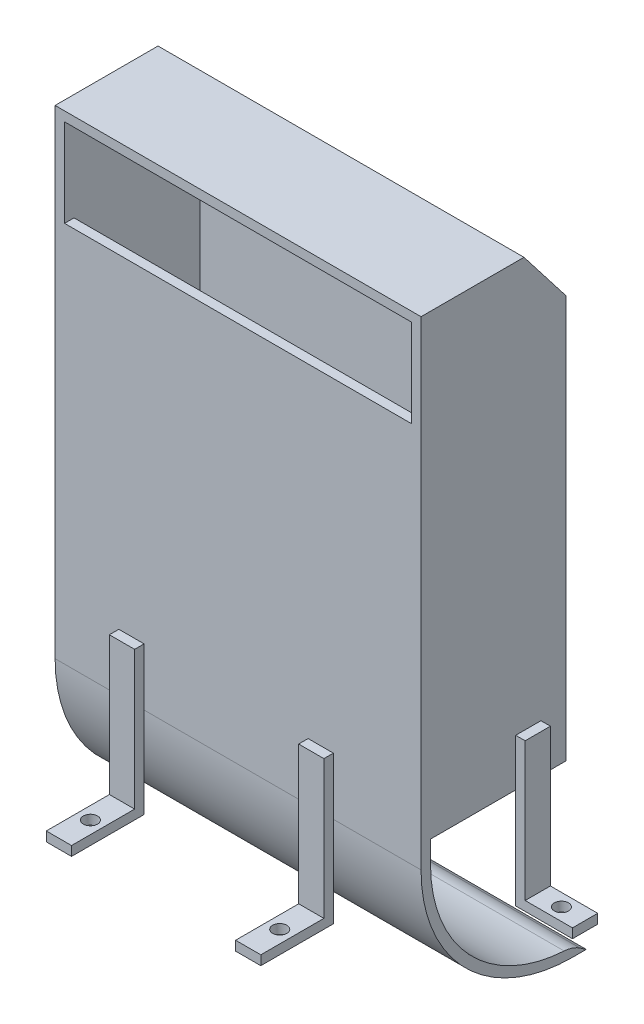
SolidWorks part; units mm, degrees
ref_plane "Front Plane" through (0, 0, 0) normal (0, 0, 1) x (1, 0, 0)
ref_plane "Top Plane" through (0, 0, 0) normal (0, 1, 0) x (1, 0, 0)
ref_plane "Right Plane" through (0, 0, 0) normal (1, 0, 0) x (0, 0, -1)
sketch "Sketch1" plane through (0, 0, 0) normal (1, 0, 0) x (0, 0, -1)
  line L0 (0, 0) -> (0, 121)
  line L1 (3, 0) -> (3, 121)
  line L2 (48, -45) -> (52.3715, -48)
  line L3 (52.3715, -48) -> (48, -48)
  line L4 (3, 121) -> (0, 121)
  arc A0 (0, 0) -> (48, -48) centre (48, 0) ccw
  arc A1 (3, 0) -> (48, -45) centre (48, 0) ccw
  dimension "D2" = 45
  dimension "D3" = 121
  dimension "D1" = 3
extrude "Boss-Extrude1" add sketch "Sketch1" along normal blind 116
sketch "Sketch2" plane through (0, 0, -3) normal (0, 0, -1) x (-1, 0, 0)
  line L1 (-116, 121) -> (-113, 121)
  line L2 (-116, 121) -> (-116, 6.9609)
  line L3 (-116, 6.9609) -> (-113, 6.9609)
  line L4 (-113, 121) -> (-113, 6.9609)
  line L5 (0, 0) -> (0, 121) construction
  line L6 (0, 121) -> (-3, 121)
  line L7 (0, 121) -> (0, 6.9609)
  line L8 (0, 6.9609) -> (-3, 6.9609)
  line L9 (-3, 121) -> (-3, 6.9609)
  line L10 (-116, 121) -> (0, 121) construction
  dimension "D1" = 3
  dimension "D2" = 3
extrude "Boss-Extrude2" add sketch "Sketch2" along normal blind 40
sketch "Sketch3" plane through (0, 0, -43) normal (0, 0, -1) x (-1, 0, 0)
  line L1 (-116, 121) -> (0, 121)
  line L2 (-116, 121) -> (-116, 6.9609)
  line L3 (-116, 6.9609) -> (0, 6.9609)
  line L4 (0, 121) -> (0, 6.9609)
extrude "Boss-Extrude3" add sketch "Sketch3" along normal blind 3
sketch "Sketch5" plane through (116, 0, 0) normal (1, 0, 0) x (0, 0, -1)
  line L0 (43, 134.156) -> (31.6048, 148.8762)
  line L1 (46, 121) -> (46, 134.5949)
  line L2 (31.6048, 148.8762) -> (0, 148.8762)
  line L3 (0, 148.8762) -> (0, 151.8762)
  line L4 (0, 151.8762) -> (32.6221, 151.8762)
  line L5 (32.6221, 151.8762) -> (46, 134.5949)
  line L6 (0, 121) -> (0, 0) construction
  line L7 (43, 134.156) -> (43, 121)
  line L8 (46, 121) -> (0, 121) construction
  line L9 (43, 121) -> (46, 121)
  dimension "D1" = 3
  dimension "D2" = 3
extrude "Boss-Extrude4" add sketch "Sketch5" against normal blind 116
sketch "Sketch6" plane through (116, 0, 0) normal (1, 0, 0) x (0, 0, -1)
  line L2 (0, 148.8762) -> (31.6048, 148.8762) construction
  line L5 (0, 148.8762) -> (31.6048, 148.8762)
  line L6 (0, 148.8762) -> (0, 121)
  line L7 (43, 121) -> (0, 121) construction
  line L8 (43, 134.156) -> (43, 121) construction
  line L9 (31.6048, 148.8762) -> (43, 134.156) construction
  line L10 (43, 121) -> (0, 121)
  line L11 (43, 134.156) -> (43, 121)
  line L12 (31.6048, 148.8762) -> (43, 134.156)
extrude "Boss-Extrude5" add sketch "Sketch6" against normal blind 3
sketch "Sketch7" plane through (0, 0, 0) normal (-1, 0, 0) x (0, 0, 1)
  line L8 (-31.6048, 148.8762) -> (0, 148.8762) construction
  line L9 (-43, 134.156) -> (-31.6048, 148.8762) construction
  line L10 (0, 148.8762) -> (0, 121) construction
  line L11 (-31.6048, 148.8762) -> (0, 148.8762)
  line L12 (-43, 134.156) -> (-31.6048, 148.8762)
  line L13 (0, 148.8762) -> (0, 121)
  line L14 (0, 121) -> (-43, 121)
  line L15 (-43, 121) -> (-43, 134.156)
extrude "Boss-Extrude6" add sketch "Sketch7" against normal blind 3
fillet "Fillet6" radius 10 1 edges at (58, -45, -48)
sketch "Sketch8" plane through (0, 6.9609, 0) normal (0, -1, 0) x (1, 0, 0)
  line L0 (0, -46) -> (0, -3) construction
  line L1 (0, -38) -> (-3, -38)
  line L2 (0, -38) -> (0, -30)
  line L3 (0, -30) -> (-3, -30)
  line L4 (-3, -38) -> (-3, -30)
  line L5 (116, -46) -> (116, -3) construction
  line L6 (116, -30) -> (119, -30)
  line L7 (116, -30) -> (116, -38)
  line L8 (116, -38) -> (119, -38)
  line L9 (119, -30) -> (119, -38)
  line L10 (116, -46) -> (0, -46) construction
  line L12 (92, 3.7948) -> (84, 3.7948)
  line L13 (92, 3.7948) -> (92, 6.7948)
  line L14 (92, 6.7948) -> (84, 6.7948)
  line L15 (84, 3.7948) -> (84, 6.7948)
  line L16 (32, 3.7948) -> (24, 3.7948)
  line L17 (32, 3.7948) -> (32, 6.7948)
  line L18 (32, 6.7948) -> (24, 6.7948)
  line L19 (24, 3.7948) -> (24, 6.7948)
  dimension "D1" = 8
  dimension "D2" = 3
  dimension "D3" = 8
  dimension "D4" = 3
  dimension "D5" = 8
  dimension "D6" = 3
  dimension "D7" = 3
  dimension "D8" = 8
  dimension "D9" = 8
  dimension "D10" = 24
  dimension "D11" = 24
extrude "Boss-Extrude7" add sketch "Sketch8" along normal blind 31.86 and the other way blind 15
sketch "Sketch9" plane through (-3, 0, 0) normal (-1, 0, 0) x (0, 0, 1)
  line L0 (-30, 21.9609) -> (-30, -24.8991) construction
  line L1 (-38, -24.8991) -> (-30, -24.8991)
  line L2 (-38, -24.8991) -> (-38, -21.8991)
  line L3 (-38, -21.8991) -> (-30, -21.8991)
  line L4 (-30, -24.8991) -> (-30, -21.8991)
  dimension "D1" = 3
extrude "Boss-Extrude8" add sketch "Sketch9" along normal blind 15
sketch "Sketch10" plane through (119, 0, 0) normal (1, 0, 0) x (0, 0, -1)
  line L0 (38, 21.9609) -> (38, -24.8991) construction
  line L1 (30, -24.8991) -> (38, -24.8991)
  line L2 (30, -24.8991) -> (30, -21.8991)
  line L3 (30, -21.8991) -> (38, -21.8991)
  line L4 (38, -24.8991) -> (38, -21.8991)
  dimension "D1" = 3
extrude "Boss-Extrude9" add sketch "Sketch10" along normal blind 15
sketch "Sketch11" plane through (0, -21.8991, 0) normal (0, 1, 0) x (1, 0, 0)
  line L1 (-18, 30) -> (-3, 30) construction
  line L2 (134, 30) -> (119, 30) construction
  line L3 (134, 38) -> (134, 30) construction
  circle A0 centre (126.5, 34) radius 2.25
  circle A1 centre (-10.5, 33.6325) radius 2.25
  point P4 (0, 0)
  point P5 (-11.1027, 33.6325)
  point P8 (-10.5, 30)
  point P14 (126.5, 30)
  point P17 (134, 34)
  dimension "D1" = 4.5
  dimension "D2" = 4.5
extrude "Cut-Extrude1" cut sketch "Sketch11" against normal blind 15
sketch "Sketch12" plane through (0, 0, 6.7948) normal (0, 0, 1) x (1, 0, 0)
  line L0 (24, 21.9609) -> (24, -24.8991) construction
  line L1 (32, -24.8991) -> (24, -24.8991)
  line L2 (32, -24.8991) -> (32, -21.8991)
  line L3 (32, -21.8991) -> (24, -21.8991)
  line L4 (24, -24.8991) -> (24, -21.8991)
  line L5 (92, 21.9609) -> (92, -24.8991) construction
  line L6 (84, -24.8991) -> (92, -24.8991)
  line L7 (84, -24.8991) -> (84, -21.8991)
  line L8 (84, -21.8991) -> (92, -21.8991)
  line L9 (92, -24.8991) -> (92, -21.8991)
  dimension "D1" = 3
  dimension "D2" = 3
extrude "Boss-Extrude10" add sketch "Sketch12" along normal blind 20
sketch "Sketch13" plane through (0, -21.8991, 0) normal (0, 1, 0) x (1, 0, 0)
  line L0 (32, -26.7948) -> (32, -6.7948) construction
  line L1 (32, -26.7948) -> (24, -26.7948) construction
  line L2 (92, -26.7948) -> (84, -26.7948) construction
  line L3 (92, -26.7948) -> (92, -6.7948) construction
  circle A0 centre (28, -16.7948) radius 2.25
  circle A1 centre (88, -16.7948) radius 2.25
  point P6 (32, -16.7948)
  point P9 (28, -26.7948)
  point P12 (88, -26.7948)
  point P15 (92, -16.7948)
  dimension "D1" = 4.5
  dimension "D2" = 4.5
extrude "Cut-Extrude2" cut sketch "Sketch13" against normal blind 20
